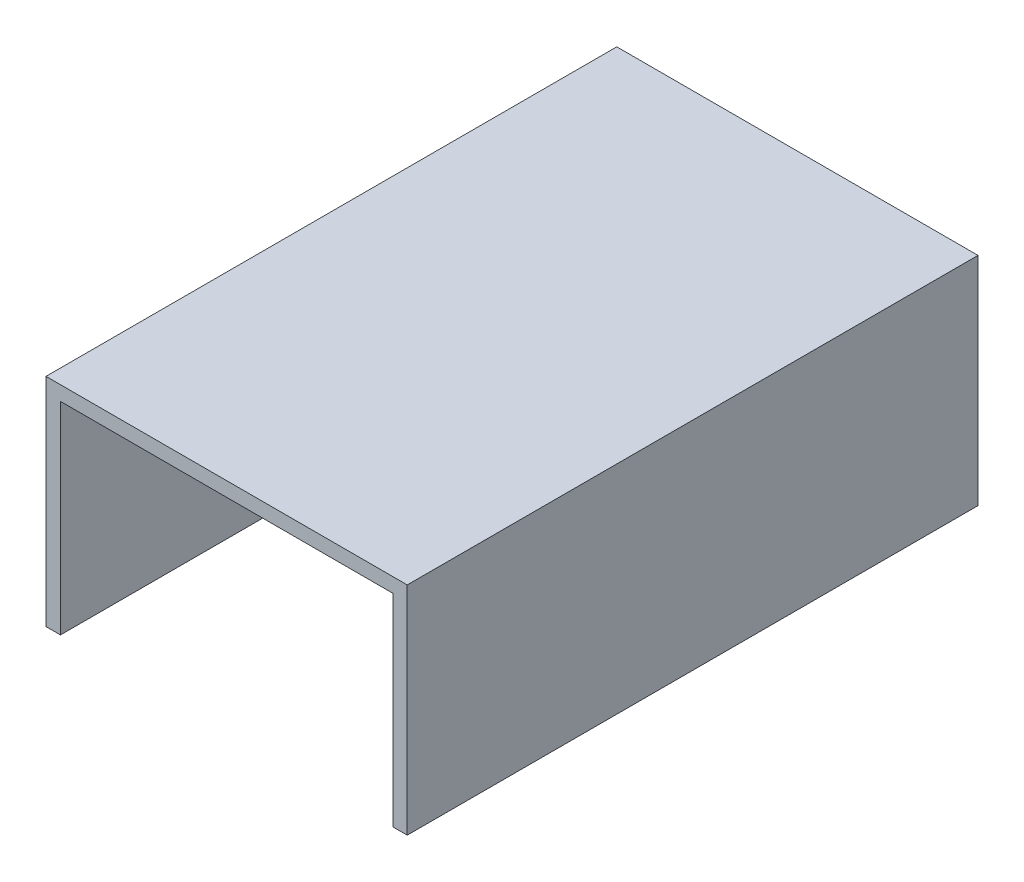
SolidWorks part; units mm, degrees
material "Custom Plastic"
ref_plane "Front Plane" through (0, 0, 0) normal (0, 0, 1) x (1, 0, 0)
ref_plane "Top Plane" through (0, 0, 0) normal (0, 1, 0) x (1, 0, 0)
ref_plane "Right Plane" through (0, 0, 0) normal (1, 0, 0) x (0, 0, -1)
sketch "Sketch1" plane through (0, 0, 0) normal (0, 0, 1) x (1, 0, 0)
  line L0 (0, 0) -> (0, 28)
  line L1 (0, 28) -> (46, 28)
  line L2 (46, 28) -> (46, 0)
  line L3 (16, 0) -> (16, 28) construction
  line L4 (0, 28) -> (46, 28) construction
  line L5 (46, 0) -> (46, 28) construction
extrude "Extrude-Thin1" add sketch "Sketch1" against normal blind 79 thin thin type one direction reverse wall 2
